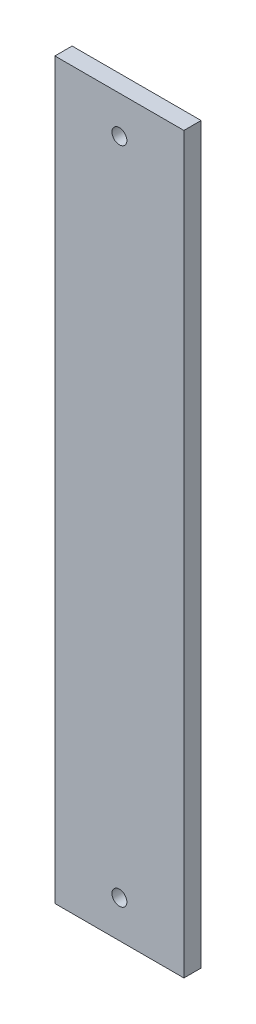
SolidWorks part; units mm, degrees
material "MDF"
ref_plane "Plano frontal" through (0, 0, 0) normal (0, 0, 1) x (1, 0, 0)
ref_plane "Plano superior" through (0, 0, 0) normal (0, 1, 0) x (1, 0, 0)
ref_plane "Plano direito" through (0, 0, 0) normal (1, 0, 0) x (0, 0, -1)
sketch "Esboço1" plane through (0, 0, 0) normal (0, 0, 1) x (1, 0, 0)
  line L1 (-22.5, -128) -> (22.5, -128)
  line L2 (-22.5, -128) -> (-22.5, 128)
  line L3 (-22.5, 128) -> (22.5, 128)
  line L4 (22.5, -128) -> (22.5, 128)
  line L5 (-22.5, -128) -> (22.5, 128) construction
  line L6 (-22.5, 128) -> (22.5, -128) construction
  line L7 (0, 0) -> (22.5, 0) construction
  circle A1 centre (0, 115) radius 2.6
  circle A2 centre (0, -115) radius 2.6
  point P0 (0, 0)
  point P11 (0, 128)
  dimension "D2" = 13
  dimension "D3" = 5.2
  dimension "D1" = 256
  dimension "D4" = 45
extrude "Ressalto-extrusão1" add sketch "Esboço1" along normal blind 6
